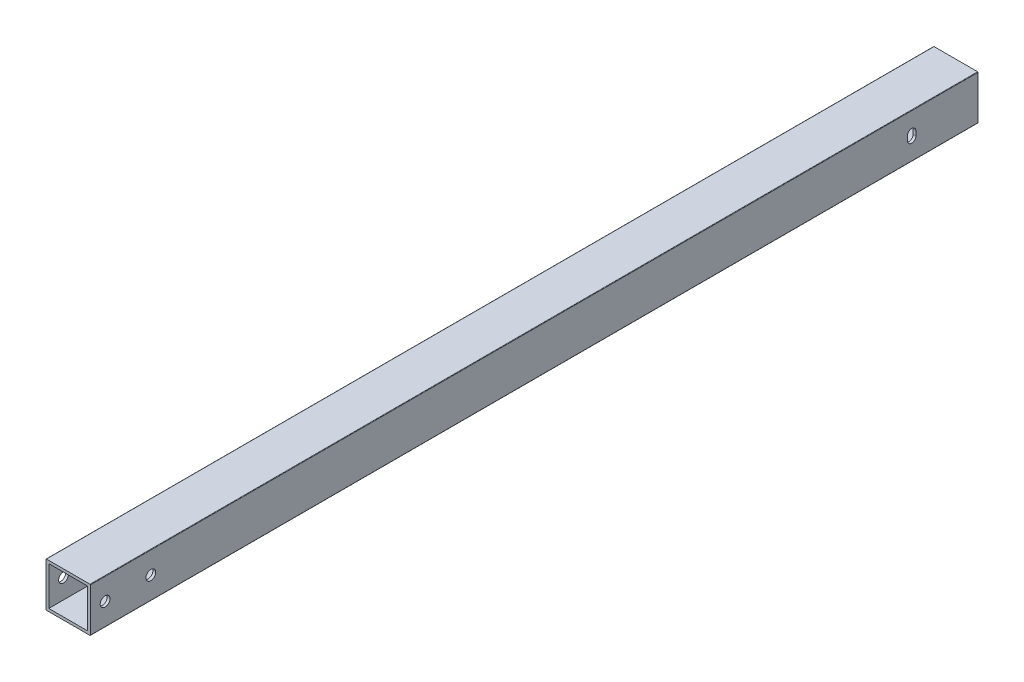
SolidWorks part; units mm, degrees
material "1060 Alloy"
ref_plane "Front Plane" through (0, 0, 0) normal (0, 0, 1) x (1, 0, 0)
ref_plane "Top Plane" through (0, 0, 0) normal (0, 1, 0) x (1, 0, 0)
ref_plane "Right Plane" through (0, 0, 0) normal (1, 0, 0) x (0, 0, -1)
ref_plane "Plane1" through (0, 0, 0) normal (0, 0, -1) x (-1, 0, 0)
sketch "Sketch1" plane through (0, 0, 0) normal (0, 0, -1) x (-1, 0, 0)
  line L4 (1.5875, -1.3335) -> (1.5875, 23.5585)
  line L5 (1.3335, 23.8125) -> (-23.5585, 23.8125)
  line L6 (-23.8125, 23.5585) -> (-23.8125, -1.3335)
  line L7 (-23.5585, -1.5875) -> (1.3335, -1.5875)
  line L9 (0, 22.225) -> (-22.225, 22.225)
  line L10 (0, 22.225) -> (0, 0)
  line L11 (0, 0) -> (-22.225, 0)
  line L12 (-22.225, 22.225) -> (-22.225, 0)
  line L13 (0, 22.225) -> (-22.225, 0) construction
  line L14 (0, 0) -> (-22.225, 22.225) construction
  arc A4 (1.3335, -1.5875) -> (1.5875, -1.3335) centre (1.3335, -1.3335) ccw
  arc A5 (1.5875, 23.5585) -> (1.3335, 23.8125) centre (1.3335, 23.5585) ccw
  arc A6 (-23.5585, 23.8125) -> (-23.8125, 23.5585) centre (-23.5585, 23.5585) ccw
  arc A7 (-23.8125, -1.3335) -> (-23.5585, -1.5875) centre (-23.5585, -1.3335) ccw
  point P24 (-11.1125, 11.1125)
  dimension "D1" = 25.4
  dimension "D2" = 25.4
  dimension "D3" = 1.5875
  dimension "D4" = 1.5875
  dimension "D5" = 1.5875
extrude "Boss-Extrude1" add sketch "Sketch1" against normal blind 508
sketch "Sketch2" plane through (-1.5875, 0, 0) normal (-1, 0, 0) x (0, 0, 1)
  line L0 (0, -1.3335) -> (0, 23.5585) construction
  line L1 (508, -1.3335) -> (0, -1.3335) construction
  line L2 (508, -1.3335) -> (508, 23.5585) construction
  circle A0 centre (12.6975, 11.3665) radius 1.5875
  circle A1 centre (495.3, 11.3665) radius 1.5875
  circle A2 centre (76.2, 11.3665) radius 6.35
  circle A3 centre (431.8, 11.3665) radius 6.35
  point P4 (0, 11.1125)
  dimension "D1" = 3.175
  dimension "D2" = 12.7
  dimension "D3" = 12.7
  dimension "D4" = 3.175
  dimension "D5" = 12.7
  dimension "D6" = 12.7
  dimension "D7" = 12.7
  dimension "D8" = 12.7
  dimension "D9" = 76.2
  dimension "D10" = 12.7
  dimension "D11" = 12.7
  dimension "D12" = 76.2
extrude "Cut-Extrude1" [suppressed] cut sketch "Sketch2" against normal through all
sketch "Sketch4" plane through (23.8125, 0, 0) normal (1, 0, 0) x (0, 0, -1)
  line L2 (-40.3145, 9.8425) -> (-40.3145, 12.3825)
  line L4 (-35.552, 9.8425) -> (-35.552, 12.3825)
  line L6 (-40.3145, 12.3825) -> (-35.552, 12.3825)
  line L7 (-40.3145, 11.1125) -> (-35.552, 11.1125)
  line L8 (0, 23.5585) -> (0, -1.3335) construction
  line L9 (0, 11.1125) -> (-49.6378, 11.1125)
  circle A0 centre (-37.9333, 9.8425) radius 2.3812
  circle A1 centre (-37.9333, 12.3825) radius 2.3812
  dimension "D1" = 4.7625
  dimension "D2" = 37.9333
  dimension "D3" = 1.27
extrude "Cut-Extrude2" cut sketch "Sketch4" against normal through all contours L6 A1 | L6 A1 A0 | L9 A0 | L9 A1 | A1 A0 | A0 L4 L7 | A1 L7 L4 | A0 L7 L2 | A1 L2 L7 | A0 region at (23.8125, 9.1445, 37.9333) region at (23.8125, 10.8001, 40.2061) region at (23.8125, 11.4249, 40.2061) region at (23.8125, 10.8001, 35.6605) region at (23.8125, 11.5673, 37.9333) region at (23.8125, 11.7352, 40.1736) region at (23.8125, 10.6577, 37.9333) region at (23.8125, 13.3931, 37.9333) region at (23.8125, 11.4249, 35.6605)
sketch "Sketch5" plane through (23.8125, 0, 0) normal (1, 0, 0) x (0, 0, -1)
  circle A0 centre (-499.5773, 11.171) radius 2.794
  circle A1 centre (-473.4153, 11.171) radius 2.794
extrude "Cut-Extrude3" cut sketch "Sketch5" against normal blind 25.4
